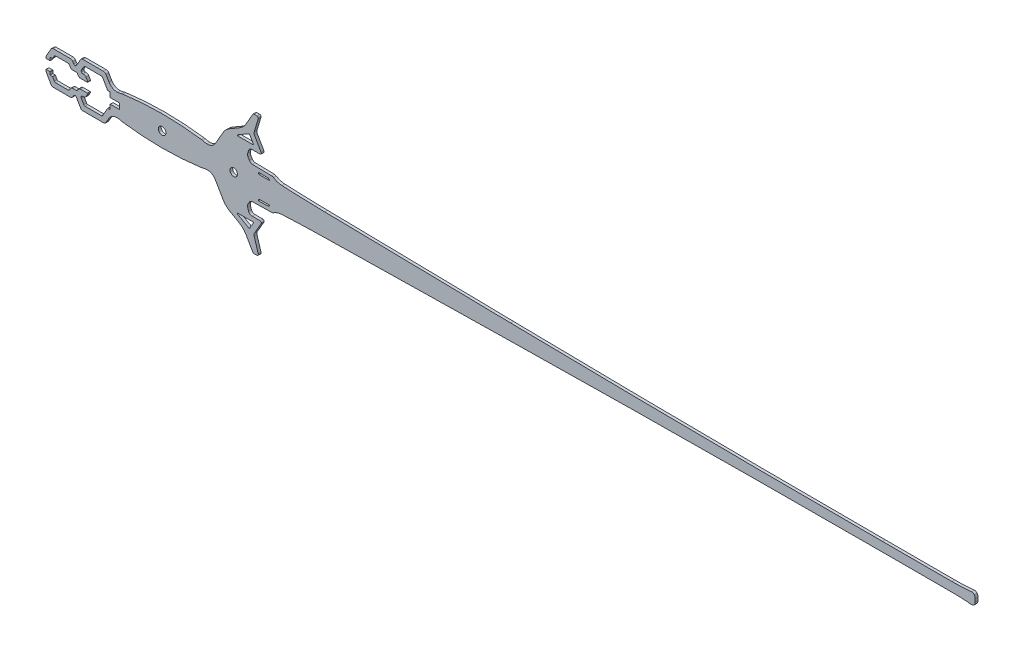
SolidWorks part; units mm, degrees
ref_plane "前视基准面" through (0, 0, 0) normal (0, 0, 1) x (1, 0, 0)
ref_plane "上视基准面" through (0, 0, 0) normal (0, 1, 0) x (1, 0, 0)
ref_plane "右视基准面" through (0, 0, 0) normal (1, 0, 0) x (0, 0, -1)
ref_axis "基准轴1" through (-243.0479, 0, 0) along (1, 0, 0)
sketch "草图1" plane through (0, 0, 0) normal (0, 0, 1) x (1, 0, 0)
  line L0 (-19.6441, 0) -> (19.6441, 0) construction
  line L1 (9, 65) -> (3.5939, 47)
  line L2 (3.5939, 47) -> (12.8315, 31)
  line L3 (12.8315, 31) -> (-1.2116, 31)
  line L4 (-1.2116, 31) -> (-3.4641, 23.5)
  line L5 (-7.7942, 31) -> (10.1036, 0)
  line L6 (80, -12) -> (280, -8.4999)
  line L7 (0, -17.5) -> (24, -17)
  line L9 (-1.2116, -31) -> (-3.4641, -23.5)
  line L10 (12.8315, -31) -> (-1.2116, -31)
  line L11 (3.5939, -47) -> (12.8315, -31)
  line L12 (9, -65) -> (3.5939, -47)
  line L13 (9, 65) -> (3, 65)
  line L14 (3, 65) -> (-7.3923, 47)
  line L15 (-7.3923, 47) -> (-26.859, 35.7609)
  line L16 (-26.859, 35.7609) -> (-40, 13)
  line L17 (-26.859, -35.7609) -> (-40, -13)
  line L18 (-7.3923, -47) -> (-26.859, -35.7609)
  line L19 (3, -65) -> (-7.3923, -47)
  line L20 (9, -65) -> (3, -65)
  line L21 (-95, 16) -> (-95, -16) construction
  line L22 (-150, 13) -> (-156.3509, 24)
  line L23 (-156.3509, 24) -> (-182, 24)
  line L24 (-150, -13) -> (-156.3509, -24)
  line L25 (-156.3509, -24) -> (-182, -24)
  line L26 (-182, 24) -> (-187.7735, 14)
  line L27 (-187.7735, 14) -> (-189.7735, 14)
  line L28 (-189.7735, 14) -> (-192.0829, 18)
  line L29 (-192.0829, 18) -> (-213.7506, 18)
  line L30 (-213.7506, 18) -> (-220, 7.1756)
  line L31 (-213.7506, -18) -> (-220, -7.1756)
  line L32 (-192.0829, -18) -> (-213.7506, -18)
  line L33 (-189.7735, -14) -> (-192.0829, -18)
  line L34 (-187.7735, -14) -> (-189.7735, -14)
  line L35 (-182, -24) -> (-187.7735, -14)
  line L36 (0, 17.5) -> (0, -17.5) construction
  line L37 (0, 17.5) -> (24, 17)
  line L38 (80, 12) -> (280, 8.4999)
  line L39 (680, 5) -> (755, 5)
  line L40 (680, -5) -> (755, -5)
  line L41 (780, 1.5) -> (780, -1.5)
  line L42 (3.5939, 36) -> (-1.1658, 44.244)
  line L43 (-1.1658, 44.244) -> (-15.4449, 36)
  line L44 (-15.4449, 36) -> (3.5939, 36)
  line L45 (-1.1658, -44.244) -> (-15.4449, -36)
  line L46 (3.5939, -36) -> (-1.1658, -44.244)
  line L47 (-15.4449, -36) -> (3.5939, -36)
  line L48 (-7.7942, 31) -> (-29.6077, 31)
  line L49 (-7.7942, -31) -> (-29.6077, -31)
  line L50 (-7.7942, -31) -> (0, -17.5)
  line L53 (-195.2583, -12.5) -> (-210.5751, -12.5)
  line L62 (-210.5751, -12.5) -> (-213, -8.3)
  line L77 (-195.2583, 12.5) -> (-210.5751, 12.5)
  line L80 (-210.5751, 12.5) -> (-213, 8.3)
  line L108 (-182.4145, -12.2821) -> (-178.8246, -18.5)
  line L109 (-178.8246, -18.5) -> (-159.5263, -18.5)
  line L110 (-159.5263, -18.5) -> (-153.6373, -8.3)
  line L111 (-153.6373, -8.3) -> (-153.6373, -3.05) construction
  line L115 (-182.4145, 12.2821) -> (-178.8246, 18.5)
  line L116 (-178.8246, 18.5) -> (-159.5263, 18.5)
  line L117 (-159.5263, 18.5) -> (-153.6373, 8.3)
  line L118 (-184.5899, -5.05) -> (-186.5818, -8.5)
  line L119 (-186.5818, -8.5) -> (-192.9489, -8.5)
  line L120 (-192.9489, -8.5) -> (-195.2583, -12.5)
  line L123 (-192.9489, 8.5) -> (-195.2583, 12.5)
  line L124 (-182.4145, -12.2821) -> (-181.4145, -10.55)
  line L125 (-181.4145, -10.55) -> (-177.8127, -10.55)
  line L126 (-177.8127, -10.55) -> (-174.6373, -5.05)
  line L127 (-174.6373, -5.05) -> (-184.5899, -5.05)
  line L128 (-186.5818, 8.5) -> (-192.9489, 8.5)
  line L129 (-177.8127, 10.55) -> (-174.6373, 5.05)
  line L130 (-174.6373, 5.05) -> (-184.5899, 5.05)
  line L131 (-184.5899, 5.05) -> (-186.5818, 8.5)
  line L132 (-182.4145, 12.2821) -> (-181.4145, 10.55)
  line L133 (-181.4145, 10.55) -> (-177.8127, 10.55)
  line L135 (-220, 7.1756) -> (-220, 5.05)
  line L136 (-213, 8.3) -> (-215.5, 8.3)
  line L137 (-215.5, 8.3) -> (-215.5, 5.05)
  line L138 (-215.5, 5.05) -> (-220, 5.05)
  line L139 (-215.5, -5.05) -> (-220, -5.05)
  line L140 (-215.5, -8.3) -> (-215.5, -5.05)
  line L141 (-213, -8.3) -> (-215.5, -8.3)
  line L142 (-150.9373, -3.05) -> (-140.6373, -3.05)
  line L143 (-140.6373, -3.05) -> (-140.6373, 3.05)
  line L144 (-220, 5.05) -> (-220, 0) construction
  line L145 (-220, -5.05) -> (-220, -7.1756)
  line L146 (-150.9373, 3.05) -> (-140.6373, 3.05)
  line L147 (-220, 0) -> (-220, -5.05) construction
  line L148 (-153.6373, -3.05) -> (-153.6373, 0) construction
  line L149 (-153.6373, 3.05) -> (-153.6373, 8.3) construction
  line L150 (-153.6373, 0) -> (-153.6373, 3.05) construction
  line L151 (-130, -14.0157) -> (-130, 14.0157)
  line L152 (-153.6373, -8.3) -> (-150.9373, -8.3)
  line L153 (-150.9373, -8.3) -> (-150.9373, -3.05)
  line L154 (-153.6373, 8.3) -> (-150.9373, 8.3)
  line L155 (-150.9373, 8.3) -> (-150.9373, 3.05)
  line L156 (-153.6373, -3.05) -> (-150.9373, -3.05) construction
  line L157 (-153.6373, 3.05) -> (-150.9373, 3.05) construction
  line L158 (-7.7942, -31) -> (10.1036, 0)
  line L159 (8.1818, -13.3287) -> (9.2376, -11.5)
  line L160 (9.2376, -11.5) -> (21.411, -11.5)
  line L161 (8.1818, -13.3287) -> (19.241, -13.0983)
  line L162 (8.1818, 13.3287) -> (19.241, 13.0983)
  line L163 (8.1818, 13.3287) -> (9.2376, 11.5)
  line L164 (9.2376, 11.5) -> (21.411, 11.5)
  arc A0 (-40, 13) -> (-52, 13) centre (-46, 30.5) cw
  arc A1 (-40, -13) -> (-52, -13) centre (-46, -30.5) ccw
  arc A2 (-52, 13) -> (-138, 13) centre (-95, -293.6667) ccw
  arc A3 (-52, -13) -> (-138, -13) centre (-95, 293.6667) cw
  arc A4 (-150, -13) -> (-138, -13) centre (-144, -30.5) cw
  arc A5 (-150, 13) -> (-138, 13) centre (-144, 30.5) ccw
  arc A6 (24, 17) -> (34, 13.5) centre (34.8863, 32.0679) ccw
  arc A7 (34, 13.5) -> (80, 12) centre (106.6708, 1535.9884) ccw
  arc A8 (34, -13.5) -> (80, -12) centre (106.6708, -1535.9884) cw
  arc A9 (24, -17) -> (34, -13.5) centre (34.8863, -32.0679) cw
  arc A10 (280, 8.4999) -> (680, 5) centre (680, 22864.7678) ccw
  arc A11 (280, -8.4999) -> (680, -5) centre (680, -22864.7678) cw
  circle A13 centre (-95, 0) radius 4.05
  circle A14 centre (-18, 0) radius 4.05
  arc A15 (780, -1.5) -> (779.2, -4.3852) centre (774.3972, -1.5) cw
  arc A16 (779.2, -4.3852) -> (776, -6) centre (776.3193, -2.6547) cw
  arc A17 (776, -6) -> (755, -5) centre (755, -226) ccw
  arc A18 (776, 6) -> (755, 5) centre (755, 226) cw
  arc A19 (779.2, 4.3852) -> (776, 6) centre (776.3193, 2.6547) ccw
  arc A20 (780, 1.5) -> (779.2, 4.3852) centre (774.3972, 1.5) ccw
  arc A21 (19.241, -13.0983) -> (21.411, -11.5) centre (34.8863, -32.0679) cw
  arc A22 (19.241, 13.0983) -> (21.411, 11.5) centre (34.8863, 32.0679) ccw
  point P30 (-46, 12)
  point P31 (-46, -12)
  point P117 (-140.6373, 0)
  dimension "D4" = 24
  dimension "D5" = 24
  dimension "D15" = 34
  dimension "D17" = 16.6
  dimension "D59" = 8.1
  dimension "D60" = 8.1
  dimension "D62" = 25
  dimension "D18" = 0.8
  dimension "D67" = 4
  dimension "D69" = 6
  dimension "D1" = 130
  dimension "D2" = 35
  dimension "D3" = 120
  dimension "D6" = 220
  dimension "D7" = 40
  dimension "D8" = 150
  dimension "D9" = 36
  dimension "D10" = 32
  dimension "D11" = 48
  dimension "D12" = 120
  dimension "D13" = 12
  dimension "D14" = 120
  dimension "D16" = 26
  dimension "D19" = 10
  dimension "D20" = 24
  dimension "D21" = 27
  dimension "D22" = 80
  dimension "D23" = 10
  dimension "D24" = 400
  dimension "D25" = 2
  dimension "D26" = 28
  dimension "D27" = 7
  dimension "D28" = 34
  dimension "D29" = 30
  dimension "D30" = 18
  dimension "D31" = 30
  dimension "D32" = 9
  dimension "D33" = 7.5
  dimension "D34" = 6
  dimension "D35" = 5.5
  dimension "D36" = 5.5
  dimension "D37" = 5
  dimension "D38" = 5.5
  dimension "D39" = 5.5
  dimension "D40" = 5.5
  dimension "D41" = 5.5
  dimension "D42" = 5.5
  dimension "D43" = 5.5
  dimension "D44" = 5.5
  dimension "D45" = 5.5
  dimension "D46" = 10.1
  dimension "D47" = 2
  dimension "D48" = 5.5
  dimension "D49" = 21
  dimension "D50" = 38
  dimension "D51" = 10.1
  dimension "D52" = 4.5
  dimension "D53" = 1000
  dimension "D54" = 6.1
  dimension "D55" = 16.6
  dimension "D56" = 90
  dimension "D57" = 13
  dimension "D58" = 10.3
  dimension "D61" = 18
  dimension "D63" = 3
  dimension "D64" = 4
  dimension "D65" = 12
  dimension "D66" = 100
  dimension "D68" = 5
  dimension "D70" = 11.5
extrude "凸台-拉伸1" add sketch "草图1" along normal mid plane 3 contours L6 A11 L40 L41 L39 A10 L38 A7 A6 L37 L5 L48 L16 A0 A2 A5 L22 L23 L26 L27 L28 L29 L30 L31 L32 L33 L34 L35 L25 L24 A4 A3 A1 L17 L49 L50 L7 A9 A8 | L48 L5 L4 L3 L2 L1 L13 L14 L15 L16 L44 L43 L42 | L50 L49 L17 L18 L19 L20 L12 L11 L10 L9 L45 L47 L46 | A5 L22 L23 L26 L27 L28 L29 L30 L135 L138 L137 L136 L80 L77 L123 L128 L131 L130 L129 L133 L132 L115 L116 L117 L149 L146 L143 L142 L111 L110 L109 L108 L124 L125 L126 L127 L118 L119 L120 L53 L62 L141 L140 L139 L145 L31 L32 L33 L34 L35 L25 | A3 A1 L17 L49 L50 L158 L5 L48 L16 A0 A2 L151 | L6 A11 L40 L41 L39 A10 L38 A7 A6 L37 L5 L158 L7 A9 A8 region at (5.7285, 56.1707, 0) region at (-54.0161, 0, 0) region at (314.7688, 0, 0) region at (-131.02, 0, 0) region at (-2.9063, -27.4207, 0)
fillet "圆角1" radius 4 10 edges at (3.5939, 47, 0) (3.5939, -47, 0) (24, -17, 0) (24, 17, 0) (-1.2116, -31, 0) (-1.2116, 31, 0) (-3.4641, 23.5, 0) (0, 17.5, 0) (-3.4641, -23.5, 0) (0, -17.5, 0)
fillet "圆角2" radius 1.5 6 edges at (12.8315, -31, 0) (12.8315, 31, 0) (3, 65, 0) (9, 65, 0) (3, -65, 0) (9, -65, 0)
fillet "圆角3" radius 20 4 edges at (-26.859, -35.7609, 0) (-7.3923, -47, 0) (-26.859, 35.7609, 0) (-7.3923, 47, 0)
fillet "圆角4" radius 10 8 edges at (-138, -13, 0) (-138, 13, 0) (-150, 13, 0) (-150, -13, 0) (-52, -13, 0) (-40, -13, 0) (-52, 13, 0) (-40, 13, 0)
fillet "圆角5" radius 0.5 6 edges at (-15.4449, -36, 0) (-1.1658, -44.244, 0) (3.5939, -36, 0) (-15.4449, 36, 0) (3.5939, 36, 0) (-1.1658, 44.244, 0)
fillet "圆角7" radius 1.5 18 edges at (-210.5751, 12.5, 0) (-210.5751, -12.5, 0) (-195.2583, -12.5, 0) (-186.5818, 8.5, 0) (-195.2583, 12.5, 0) (-178.8246, 18.5, 0) (-159.5263, 18.5, 0) (-159.5263, -18.5, 0) (-178.8246, -18.5, 0) (-186.5818, -8.5, 0) (-182.4145, 12.2821, 0) (-181.4145, 10.55, 0) (-181.4145, -10.55, 0) (-182.4145, -12.2821, 0) (-189.7735, -14, 0) (-187.7735, -14, 0) (-187.7735, 14, 0) (-189.7735, 14, 0)
fillet "圆角8" radius 3 14 edges at (-213.7506, 18, 0) (-213.7506, -18, 0) (-192.0829, -18, 0) (-192.0829, 18, 0) (-177.8127, 10.55, 0) (-177.8127, -10.55, 0) (-184.5899, 5.05, 0) (-192.9489, 8.5, 0) (-192.9489, -8.5, 0) (-184.5899, -5.05, 0) (-182, 24, 0) (-156.3509, 24, 0) (-156.3509, -24, 0) (-182, -24, 0)
chamfer "倒角1" distance 0.1 angle 45 10 edges at (-150.9373, 3.05, 0) (-150.9373, -3.05, 0) (-150.9373, 8.3, 0) (-150.9373, -8.3, 0) (-140.6373, 3.05, 0) (-140.6373, -3.05, 0) (-215.5, -5.05, 0) (-215.5, 5.05, 0) (-220, -5.05, 0) (-220, 5.05, 0)
fillet "圆角9" radius 0.5 2 edges at (-174.6373, 5.05, 0) (-174.6373, -5.05, 0)
fillet "圆角10" radius 0.4 8 edges at (19.241, 13.0983, 0) (21.411, 11.5, 0) (9.2376, 11.5, 0) (8.1818, 13.3287, 0) (9.2376, -11.5, 0) (8.1818, -13.3287, 0) (19.241, -13.0983, 0) (21.411, -11.5, 0)
